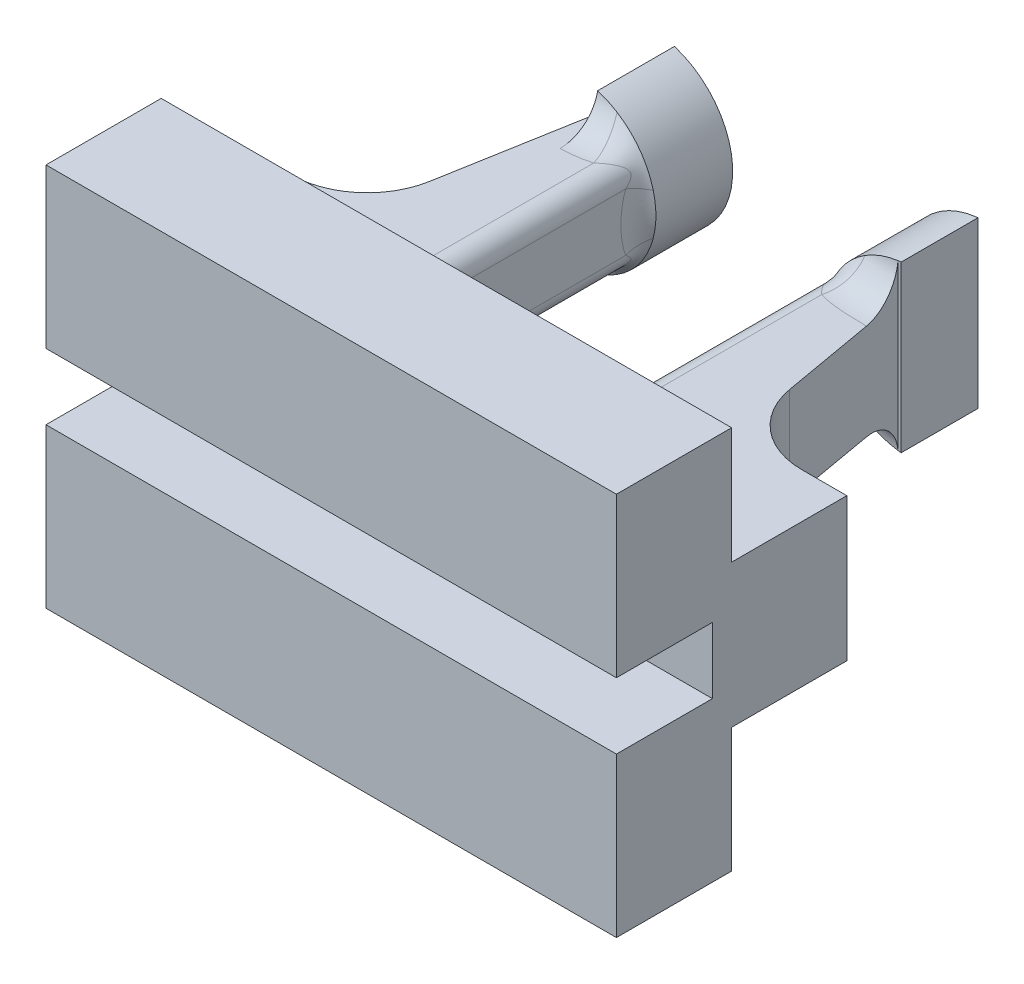
SolidWorks part; units mm, degrees
ref_plane "Alzado" through (0, 0, 0) normal (0, 0, 1) x (1, 0, 0)
ref_plane "Planta" through (0, 0, 0) normal (0, 1, 0) x (1, 0, 0)
ref_plane "Vista lateral" through (0, 0, 0) normal (1, 0, 0) x (0, 0, -1)
sketch "Croquis1" plane through (0, 0, 0) normal (0, 0, 1) x (1, 0, 0)
  line L1 (0, 0) -> (114.7688, 0)
  line L2 (0, 0) -> (0, -7.45)
  line L3 (0, -7.45) -> (114.7688, -7.45)
  line L4 (114.7688, 0) -> (114.7688, -7.45)
  dimension "D2" = 7.45
extrude "Saliente-Extruir1" add sketch "Croquis1" along normal blind 6
sketch "Croquis2" plane through (0, 0, 6) normal (0, 0, 1) x (1, 0, 0)
  line L0 (0, 0) -> (0, -7.45) construction
  line L1 (-14, 6.065) -> (128.7688, 6.065)
  line L2 (-14, 6.065) -> (-14, -13.935)
  line L3 (-14, -13.935) -> (128.7688, -13.935)
  line L4 (128.7688, 6.065) -> (128.7688, -13.935)
  line L5 (-14, 6.065) -> (128.7688, -13.935) construction
  line L6 (-14, -13.935) -> (128.7688, 6.065) construction
  line L7 (114.7688, -7.45) -> (114.7688, 0) construction
  point P0 (57.3844, -3.935)
  point P7 (-14, -3.935)
  dimension "D1" = 14
  dimension "D2" = 14
  dimension "D3" = 20
extrude "Saliente-Extruir2" add sketch "Croquis2" along normal blind 6
sketch "Croquis3" plane through (0, 0, 12) normal (0, 0, 1) x (1, 0, 0)
  line L6 (-14, 6.065) -> (-14, -13.935) construction
  line L7 (-14, -5.655) -> (128.7688, -5.655)
  line L8 (-14, -5.655) -> (-14, -2.215)
  line L9 (-14, -2.215) -> (128.7688, -2.215)
  line L10 (128.7688, -5.655) -> (128.7688, -2.215)
  line L11 (128.7688, -13.935) -> (128.7688, 6.065) construction
  line L12 (-14, -3.935) -> (128.7688, -3.935) construction
  point P10 (-14, -3.935)
  dimension "D1" = 3.44
extrude "Cortar-Extruir1" cut sketch "Croquis3" against normal blind 5
sketch "Croquis4" plane through (0, 0, 0) normal (0, 1, 0) x (1, 0, 0)
  line L0 (34.1475, 0) -> (36.6429, 14.1521)
  line L1 (114.7688, 0) -> (0, 0) construction
  line L2 (36.6429, 14.1521) -> (39.1761, 14.1521)
  line L3 (39.1761, 14.1521) -> (39.1761, 0)
  line L4 (49.0461, 14.1521) -> (49.0461, 0)
  line L5 (49.0461, 14.1521) -> (51.5792, 14.1521)
  line L6 (51.5792, 14.1521) -> (54.0746, 0)
  line L7 (34.1475, 0) -> (39.1761, 0)
  line L8 (49.0461, 0) -> (54.0746, 0)
  dimension "D1" = 9.87
  dimension "D2" = 100
  dimension "D3" = 100
extrude "Saliente-Extruir3" add sketch "Croquis4" against normal blind 5
fillet "Redondeo1" radius 4 2 edges at (34.1475, -2.5, 0) (54.0746, -2.5, 0)
fillet "Redondeo2" radius 2 2 edges at (34.9836, -5, 0) (53.2386, -5, 0)
fillet "Redondeo3" radius 1 6 edges at (49.0461, -5.5858, -0.5858) (39.1761, -5.5858, -0.5858) (49.0461, 0, -7.0761) (49.0461, -5, -8.0761) (39.1761, 0, -7.0761) (39.1761, -5, -8.0761)
sketch "Croquis5" plane through (0, 0, -14.1521) normal (0, 0, -1) x (-1, 0, 0)
  line L1 (-50.0461, -7) -> (-38.1761, 0) construction
  line L2 (-50.0461, 0) -> (-38.1761, -7) construction
  line L3 (-44.1111, 0) -> (-44.1111, -7.45) construction
  line L4 (-50.0461, 0) -> (-38.1761, 0) construction
  line L5 (0, -7.45) -> (-114.7688, -7.45) construction
  line L6 (-52.4527, 1.8018) -> (-52.4527, -6.8018)
  line L8 (-36.6429, 1.6251) -> (-36.6429, -6.6251)
  line L10 (-36.6429, -5) -> (-36.6429, 0) construction
  arc A0 (-52.4527, -6.8018) -> (-52.4527, 1.8018) centre (-52.8683, -2.5) ccw
  arc A1 (-36.6429, -6.6251) -> (-36.6429, 1.6251) centre (-35.3539, -2.5) cw
  point P22 (-52.4527, -2.5)
  point P24 (-36.6429, -2.5)
extrude "Saliente-Extruir4" add sketch "Croquis5" against normal blind 4
fillet "Redondeo4" radius 2 10 edges at (37.4095, -5, -10.1521) (38.8832, -4.7071, -10.1521) (39.1761, -2.5, -10.1521) (38.8832, -0.2929, -10.1521) (51.1653, -5, -10.1521) (49.339, -4.7071, -10.1521) (49.0461, -2.5, -10.1521) (49.339, -0.2929, -10.1521) (37.4095, 0, -10.1521) (51.1653, 0, -10.1521)
ref_plane "Plano1" through (0, 0, 12) normal (0, 0, 1) x (1, 0, 0)
sketch "Croquis6" plane through (0, 0, 12) normal (0, 0, 1) x (1, 0, 0)
  line L1 (-14, 6.065) -> (30.0618, 6.065)
  line L2 (-14, 6.065) -> (-14, -38.6498)
  line L3 (-14, -38.6498) -> (30.0618, -38.6498)
  line L4 (30.0618, 6.065) -> (30.0618, -38.6498)
  line L5 (128.7688, 6.065) -> (59.7715, 6.065)
  line L6 (128.7688, 6.065) -> (128.7688, -31.5026)
  line L7 (128.7688, -31.5026) -> (59.7715, -31.5026)
  line L8 (59.7715, 6.065) -> (59.7715, -31.5026)
  point P5 (59.7715, -31.5026)
  point P11 (30.0618, -38.6498)
extrude "Cortar-Extruir2" cut sketch "Croquis6" against normal through all
